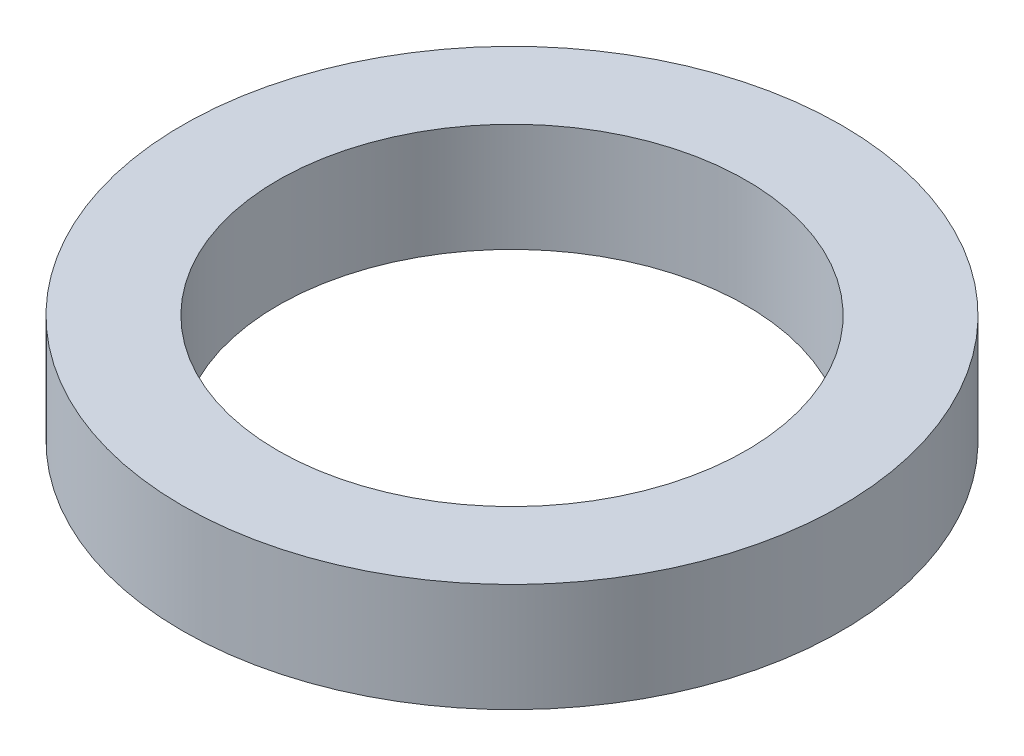
SolidWorks part; units mm, degrees
ref_plane "Front Plane" through (0, 0, 0) normal (0, 0, 1) x (1, 0, 0)
ref_plane "Top Plane" through (0, 0, 0) normal (0, 1, 0) x (1, 0, 0)
ref_plane "Right Plane" through (0, 0, 0) normal (1, 0, 0) x (0, 0, -1)
sketch "Sketch1" plane through (0, 0, 0) normal (0, 1, 0) x (1, 0, 0)
  circle A0 centre (0, 0) radius 3.429
  circle A1 centre (0, 0) radius 5.08 construction
  circle A2 centre (0, 0) radius 4.826
  dimension "D1" = 0.254
  dimension "D2" = 6.858
  dimension "D3" = 10.16
extrude "Boss-Extrude1" add sketch "Sketch1" along normal blind 1.5875
